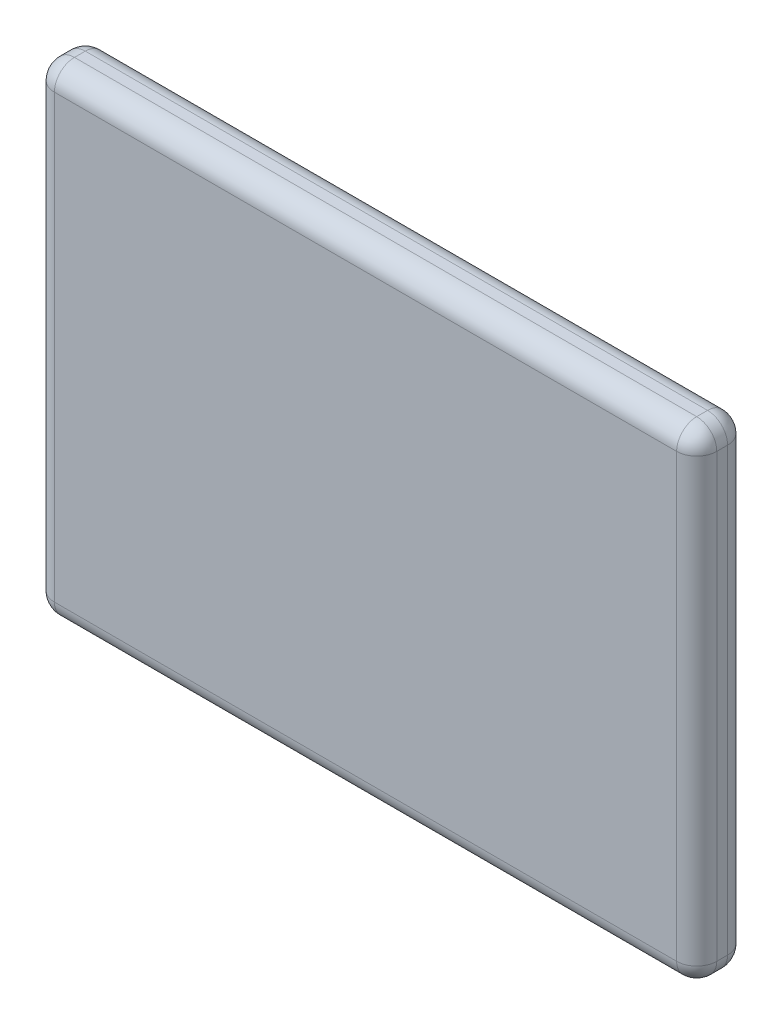
SolidWorks part; units mm, degrees
material "Polyurethane foam"
ref_plane "Front Plane" through (0, 0, 0) normal (0, 0, 1) x (1, 0, 0)
ref_plane "Top Plane" through (0, 0, 0) normal (0, 1, 0) x (1, 0, 0)
ref_plane "Right Plane" through (0, 0, 0) normal (1, 0, 0) x (0, 0, -1)
sketch "Sketch1" plane through (0, 0, 0) normal (0, 0, 1) x (1, 0, 0)
  line L1 (-371.3628, 90.7406) -> (288.6372, 90.7406)
  line L2 (-371.3628, 90.7406) -> (-371.3628, -389.2594)
  line L3 (-371.3628, -389.2594) -> (288.6372, -389.2594)
  line L4 (288.6372, 90.7406) -> (288.6372, -389.2594)
  dimension "D1" = 660
  dimension "D2" = 480
extrude "Boss-Extrude1" add sketch "Sketch1" along normal blind 50.8
fillet "Fillet1" radius 20 4 edges at (-371.3628, -149.2594, 0) (-41.3628, -389.2594, 0) (288.6372, -149.2594, 0) (-41.3628, 90.7406, 0)
fillet "Fillet2" radius 20 12 edges at (-365.505, -383.4015, 5.8579) (282.7793, -383.4015, 5.8579) (-365.505, 84.8827, 5.8579) (282.7793, 84.8827, 5.8579) (-371.3628, -149.2594, 50.8) (-41.3628, -389.2594, 50.8) (-371.3628, -389.2594, 35.4) (288.6372, -149.2594, 50.8) (288.6372, -389.2594, 35.4) (-41.3628, 90.7406, 50.8) (-371.3628, 90.7406, 35.4) (288.6372, 90.7406, 35.4)
